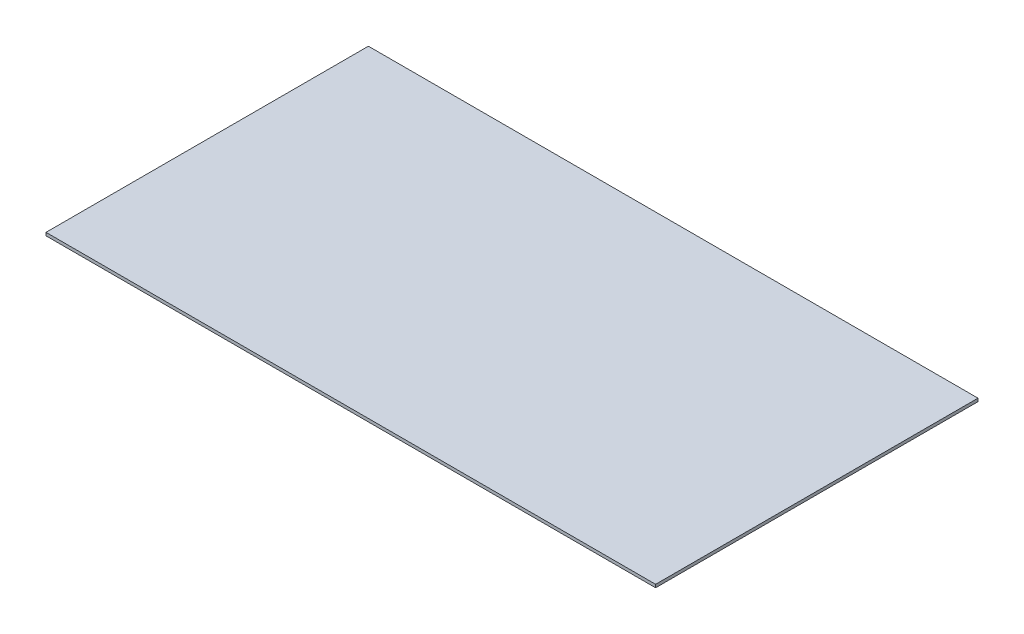
SolidWorks part; units mm, degrees
material "6061-T6 (SS)"
ref_plane "X-Y Datum" through (0, 0, 0) normal (0, 0, 1) x (1, 0, 0)
ref_plane "X-Z Datum" through (0, 0, 0) normal (0, 1, 0) x (1, 0, 0)
ref_plane "Y-Z Datum" through (0, 0, 0) normal (1, 0, 0) x (0, 0, -1)
sketch "Sketch1" plane through (0, 0, 0) normal (0, 0, 1) x (1, 0, 0)
  line L1 (-228.6, -1.143) -> (228.6, -1.143)
  line L2 (-228.6, -1.143) -> (-228.6, 1.143)
  line L3 (-228.6, 1.143) -> (228.6, 1.143)
  line L4 (228.6, -1.143) -> (228.6, 1.143)
  line L5 (-228.6, -1.143) -> (228.6, 1.143) construction
  line L6 (-228.6, 1.143) -> (228.6, -1.143) construction
  point P0 (0, 0)
  dimension "D1" = 2.286
  dimension "D2" = 457.2
extrude "Boss-Extrude1" add sketch "Sketch1" along normal blind 238.62
sketch "Sketch2" plane through (0, 0, 0) normal (0, 0, -1) x (-1, 0, 0)
  line L22 (-228.6, 1.143) -> (-228.6, -1.143)
  line L23 (-228.6, -1.143) -> (228.6, -1.143)
  line L24 (228.6, -1.143) -> (228.6, 1.143)
  line L25 (228.6, 1.143) -> (-228.6, 1.143)
  line L26 (-228.6, 1.143) -> (-228.6, -1.143)
  line L27 (-228.6, -1.143) -> (228.6, -1.143)
  line L28 (228.6, -1.143) -> (228.6, 1.143)
  line L29 (228.6, 1.143) -> (-228.6, 1.143)
  line M6 (-228.6, -1.143) -> (228.6, -1.143)
  line M8 (228.6, 1.143) -> (-228.6, 1.143)
  dimension "D1" = 0
extrude "Boss-Extrude2" add sketch "Sketch2" along normal blind 3.175 contours M8 M6 | M8 M6 region at (0, 0, 0)
